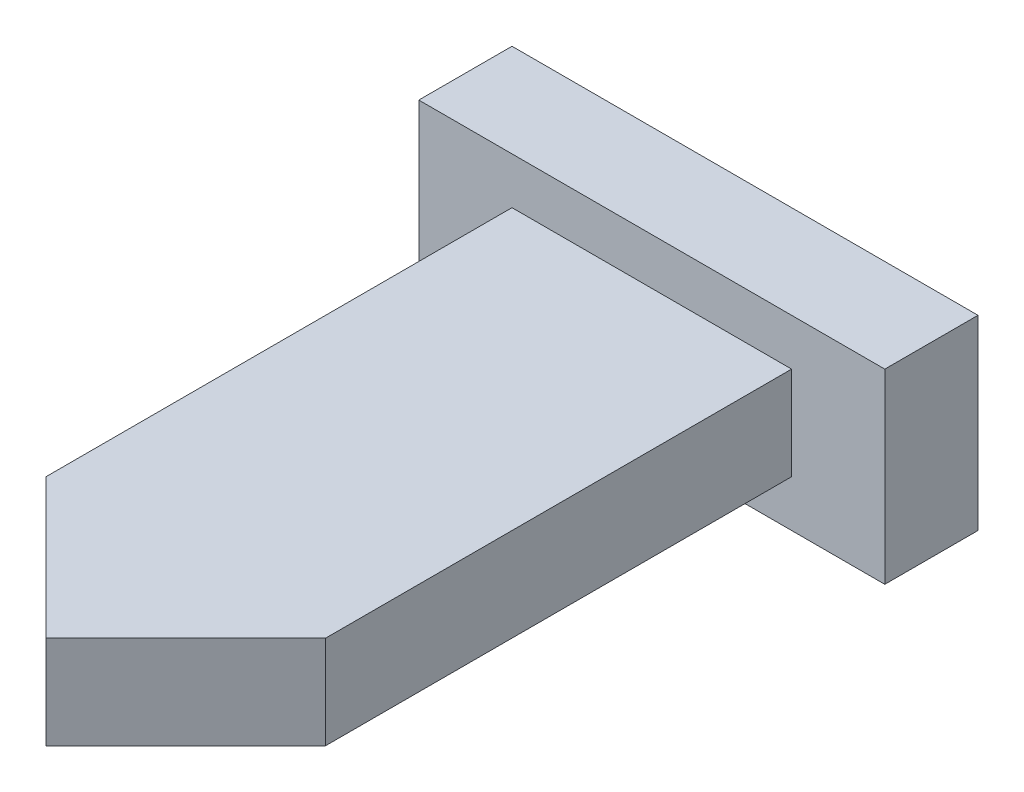
SolidWorks part; units mm, degrees
ref_plane "Front Plane" through (0, 0, 0) normal (1, 0, 0) x (0, 1, 0)
ref_plane "Top Plane" through (0, 0, 0) normal (0, 0, 1) x (0, 1, 0)
ref_plane "Right Plane" through (0, 0, 0) normal (0, 1, 0) x (-1, 0, 0)
sketch "Sketch1" plane through (0, 0, 0) normal (0, 1, 0) x (-1, 0, 0)
  line L0 (0, 0) -> (0, 50000) construction
  line L1 (0, 0) -> (50000, 0) construction
  line L2 (-37.5, 0) -> (37.5, 0)
  line L3 (37.5, 0) -> (37.5, 15)
  line L4 (37.5, 15) -> (-37.5, 15)
  line L5 (-37.5, 15) -> (-37.5, 0)
  line L6 (-22.5, 15) -> (22.5, 15)
  line L7 (22.5, 15) -> (22.5, 90)
  line L9 (-22.5, 90) -> (-22.5, 15)
  line L10 (0, 112.5) -> (-22.5, 90)
  line L11 (0, 112.5) -> (22.5, 90)
  point P8 (0, 0)
  point P13 (0, 15)
  point P14 (-22.5, 112.5)
  dimension "D1" = 45
  dimension "D2" = 75
  dimension "D3" = 15
  dimension "D4" = 75
  dimension "D6" = 90
extrude "Boss-Extrude1" add sketch "Sketch1" along normal mid plane 30 contours L4 L5 L2 L3 region at (0, 0, 7.5)
extrude "Boss-Extrude2" add sketch "Sketch1<3>" along normal mid plane 15 contours L11 L10 L9 L4 L7 region at (0, 0, 58.3696)
sketch "Sketch1<3>" plane through (0, 0, 0) normal (0, 1, 0) x (-1, 0, 0) same geometry as "Sketch1"
